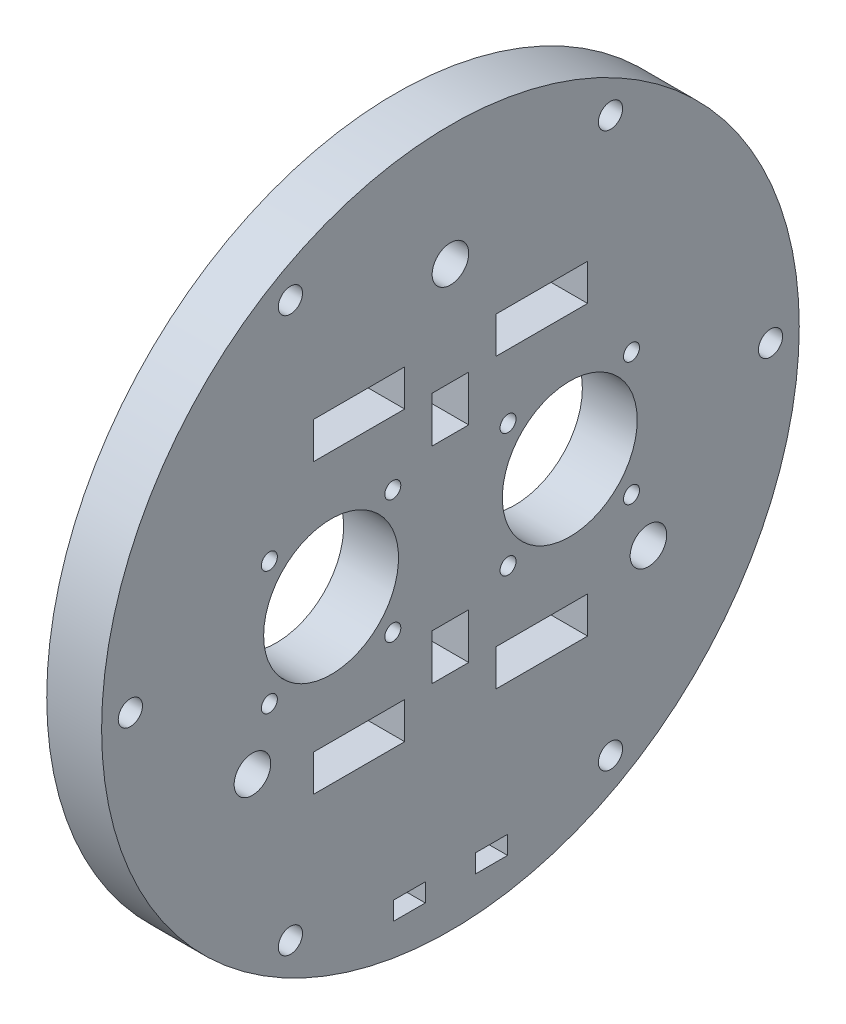
SolidWorks part; units mm, degrees
ref_plane "Front Plane" through (0, 0, 0) normal (0, 0, 1) x (1, 0, 0)
ref_plane "Top Plane" through (0, 0, 0) normal (0, 1, 0) x (1, 0, 0)
ref_plane "Right Plane" through (0, 0, 0) normal (1, 0, 0) x (0, 0, -1)
sketch "Sketch1" plane through (0, 0, 0) normal (1, 0, 0) x (0, 0, -1)
  line L0 (0, -76.29) -> (0, 76.29) construction
  line L1 (-76.29, 0) -> (76.29, 0) construction
  line L2 (26.1, 0) -> (39.5969, 13.4969) construction
  circle A0 centre (0, 0) radius 76.29
  circle A1 centre (0, 50) radius 4
  circle A2 centre (43.3013, -25) radius 4
  circle A3 centre (-43.3013, -25) radius 4
  circle A4 centre (26.1, 0) radius 14.75
  circle A5 centre (-26.1, 0) radius 14.75
  circle A6 centre (39.5969, 13.4969) radius 1.75
  circle A7 centre (39.5969, -13.4969) radius 1.75
  circle A8 centre (12.6031, -13.4969) radius 1.75
  circle A9 centre (12.6031, 13.4969) radius 1.75
  circle A10 centre (-39.5969, -13.4969) radius 1.75
  circle A11 centre (-12.6031, -13.4969) radius 1.75
  circle A12 centre (-12.6031, 13.4969) radius 1.75
  circle A13 centre (-39.5969, 13.4969) radius 1.75
  circle A14 centre (26.1, 0) radius 22.1 construction
  circle A15 centre (-26.1, 0) radius 22.1 construction
  point P12 (0, 0)
  point P29 (26.1, 0)
  point P37 (-4, 0)
  point P40 (4, 0)
  dimension "D1" = 152.58
  dimension "D2" = 8
  dimension "D5" = 29.5
  dimension "D7" = 3.5
  dimension "D11" = 44.2
  dimension "D3" = 50
  dimension "D4" = 3
  dimension "D6" = 8
  dimension "D8" = 19.0875
  dimension "D10" = 45
  dimension "D9" = 4
extrude "Boss-Extrude1" add sketch "Sketch1" along normal blind 12
sketch "Sketch2" plane through (12, 0, 0) normal (1, 0, 0) x (0, 0, -1)
  line L0 (-97.5918, 0) -> (102.3086, 0) construction
  line L1 (0, 96.3466) -> (0, -103.9448) construction
  line L2 (10, -27.5) -> (10, -35.5)
  line L3 (-30, -27.5) -> (-10, -27.5)
  line L4 (-30, -27.5) -> (-30, -35.5)
  line L5 (-30, -35.5) -> (-10, -35.5)
  line L6 (-10, -27.5) -> (-10, -35.5)
  line L7 (30, -27.5) -> (10, -27.5)
  line L8 (30, -27.5) -> (30, -35.5)
  line L9 (30, -35.5) -> (10, -35.5)
  line L10 (-30, 27.5) -> (-30, 35.5)
  line L11 (-30, 35.5) -> (-10, 35.5)
  line L12 (-10, 27.5) -> (-10, 35.5)
  line L13 (-30, 27.5) -> (-10, 27.5)
  line L14 (10, 27.5) -> (10, 35.5)
  line L15 (30, 35.5) -> (10, 35.5)
  line L16 (30, 27.5) -> (10, 27.5)
  line L17 (30, 27.5) -> (30, 35.5)
  line L18 (-4, -17.5) -> (4, -17.5)
  line L19 (-4, 27.5) -> (4, 27.5)
  line L20 (-4, 27.5) -> (-4, 17.5)
  line L21 (-4, 17.5) -> (4, 17.5)
  line L22 (4, 27.5) -> (4, 17.5)
  line L23 (-4, -27.5) -> (-4, -17.5)
  line L24 (-4, -27.5) -> (4, -27.5)
  line L25 (4, -27.5) -> (4, -17.5)
  line L26 (27.8787, -35.5) -> (30, -33.3787) construction
  line L27 (-42.3534, -68.29) -> (39.6493, -68.29) construction
  line L28 (-5.5, -68.29) -> (-5.5, -64.29)
  line L29 (12.5, -68.29) -> (5.5, -68.29)
  line L30 (12.5, -68.29) -> (12.5, -64.29)
  line L31 (12.5, -64.29) -> (5.5, -64.29)
  line L32 (5.5, -68.29) -> (5.5, -64.29)
  line L33 (-12.5, -64.29) -> (-5.5, -64.29)
  line L34 (-12.5, -68.29) -> (-12.5, -64.29)
  line L35 (-12.5, -68.29) -> (-5.5, -68.29)
  circle A0 centre (30, -35.5) radius 2.1213 construction
  circle A1 centre (0, 0) radius 76.29 construction
  point P23 (0, 27.5)
  point P31 (30, -33.3787)
  point P32 (0, -76.29)
  point P33 (27.8787, -35.5)
  dimension "D1" = 27.5
  dimension "D2" = 8
  dimension "D3" = 20
  dimension "D4" = 20
  dimension "D5" = 8
  dimension "D6" = 10
  dimension "D7" = 8
  dimension "D8" = 4
  dimension "D9" = 7
  dimension "D10" = 25
extrude "Cut-Extrude1" cut sketch "Sketch2" against normal blind 8
sketch "Sketch3" plane through (0, 0, 0) normal (-1, 0, 0) x (0, 0, 1)
  circle A0 centre (-70, 0) radius 2.65
  circle A1 centre (-35, 60.6218) radius 2.65
  circle A2 centre (35, 60.6218) radius 2.65
  circle A3 centre (70, 0) radius 2.65
  circle A4 centre (35, -60.6218) radius 2.65
  circle A5 centre (-35, -60.6218) radius 2.65
  point P16 (0, 0)
  dimension "D2" = 5.3
  dimension "D1" = 70
  dimension "D3" = 6
extrude "Cut-Extrude2" cut sketch "Sketch3" against normal up to next
